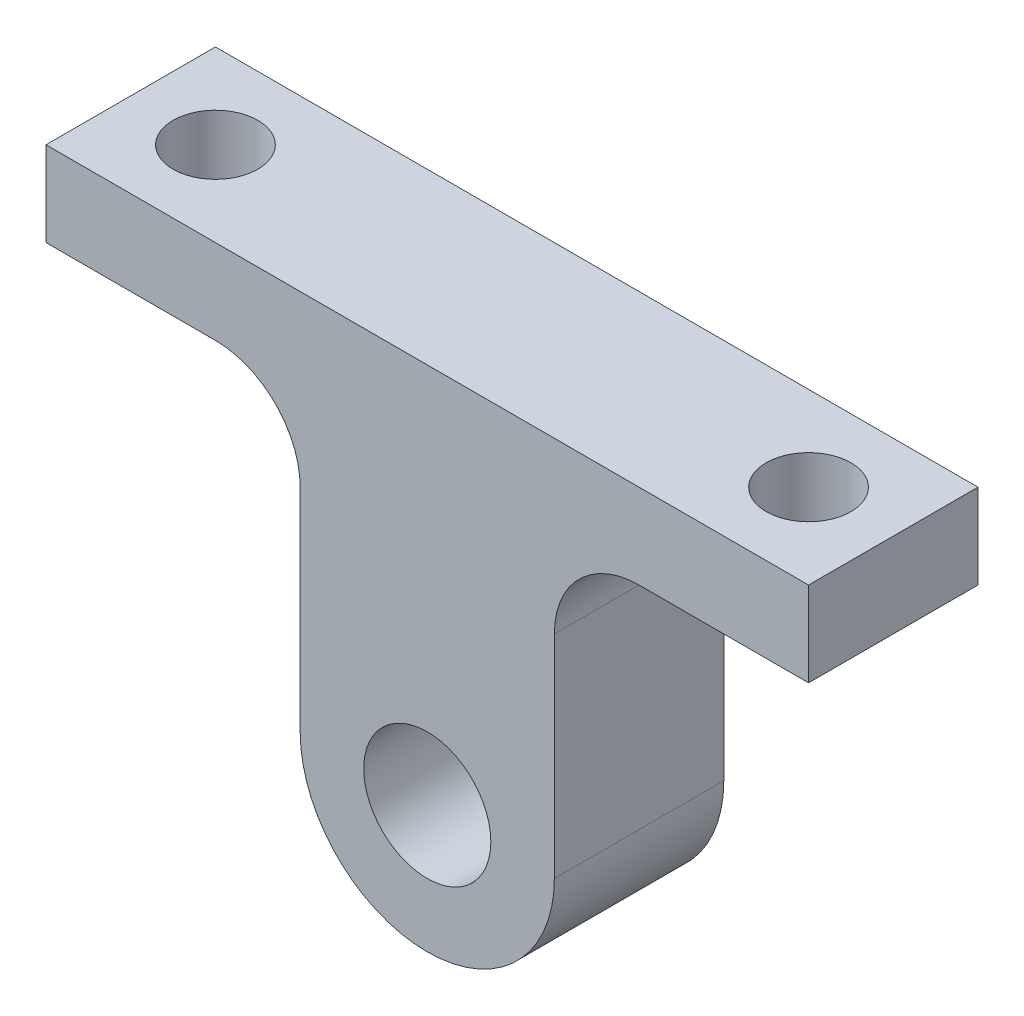
SolidWorks part; units mm, degrees
material "6061-T6 (SS)"
ref_plane "Front Plane" through (0, 0, 0) normal (0, 0, 1) x (1, 0, 0)
ref_plane "Top Plane" through (0, 0, 0) normal (0, 1, 0) x (1, 0, 0)
ref_plane "Right Plane" through (0, 0, 0) normal (1, 0, 0) x (0, 0, -1)
sketch "Sketch1" plane through (0, 0, 0) normal (0, 0, 1) x (1, 0, 0)
  line L0 (-9.525, 22.225) -> (-9.525, -9.525)
  line L1 (-9.525, -9.525) -> (9.525, -9.525)
  line L2 (9.525, -9.525) -> (9.525, 22.225)
  line L3 (9.525, 22.225) -> (28.575, 22.225)
  line L4 (28.575, 22.225) -> (28.575, 28.575)
  line L5 (28.575, 28.575) -> (-28.575, 28.575)
  line L6 (-28.575, 28.575) -> (-28.575, 22.225)
  line L7 (-28.575, 22.225) -> (-9.525, 22.225)
  circle A0 centre (0, 0) radius 4.7625
  dimension "D5" = 6.35
  dimension "D1" = 9.525
  dimension "D3" = 19.05
  dimension "D6" = 9.525
  dimension "D2" = 19.05
  dimension "D4" = 38.1
  dimension "D10" = 9.525
extrude "Boss-Extrude1" add sketch "Sketch1" along normal mid plane 12.7
sketch "Sketch2" plane through (-28.575, 0, 0) normal (-1, 0, 0) x (0, 0, 1)
  line L8 (6.35, 22.225) -> (-6.35, 22.225) construction
  line L9 (6.35, -9.525) -> (5.715, -9.525)
  line L10 (6.35, -9.525) -> (6.35, 22.225)
  line L11 (6.35, 22.225) -> (5.715, 22.225)
  line L12 (5.715, -9.525) -> (5.715, 22.225)
  line L14 (-6.35, -9.525) -> (-5.715, -9.525)
  line L15 (-6.35, -9.525) -> (-6.35, 22.225)
  line L16 (-6.35, 22.225) -> (-5.715, 22.225)
  line L17 (-5.715, -9.525) -> (-5.715, 22.225)
  dimension "D1" = 11.43
fillet "Fillet1" radius 6.35 2 edges at (9.525, 22.225, 0) (-9.525, 22.225, 0)
fillet "Fillet2" radius 9.525 2 edges at (9.525, -9.525, 0) (-9.525, -9.525, 0)
sketch "Sketch3" plane through (0, 28.575, 0) normal (0, 1, 0) x (1, 0, 0)
  line L0 (-22.225, 0) -> (22.225, 0) construction
  circle A0 centre (-22.225, 0) radius 3.175
  circle A1 centre (22.225, 0) radius 3.175
  point P4 (0, 0)
  dimension "D1" = 6.35
  dimension "D2" = 44.45
extrude "Cut-Extrude2" cut sketch "Sketch3" against normal through all
